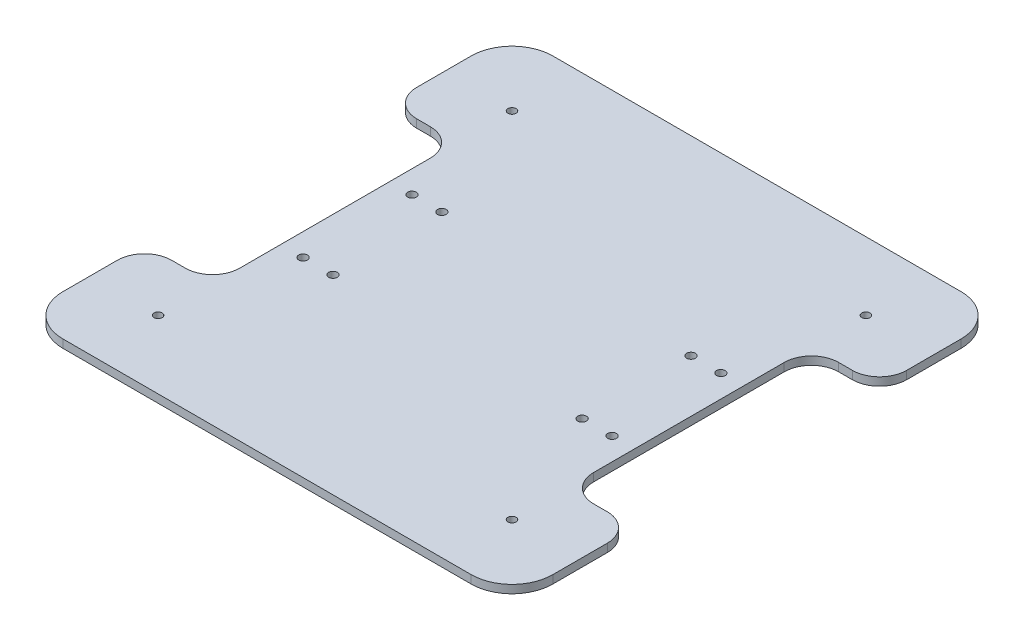
SolidWorks part; units mm, degrees
ref_plane "Спереди" through (0, 0, 0) normal (0, 0, 1) x (1, 0, 0)
ref_plane "Сверху" through (0, 0, 0) normal (0, 1, 0) x (1, 0, 0)
ref_plane "Справа" through (0, 0, 0) normal (1, 0, 0) x (0, 0, -1)
sketch "Sketch1" plane through (0, 0, 0) normal (0, 1, 0) x (1, 0, 0)
  line L1 (-90, 90) -> (90, 90)
  line L2 (-90, 90) -> (-90, -90)
  line L3 (-90, -90) -> (90, -90)
  line L4 (90, 90) -> (90, -90)
  line L5 (-90, 90) -> (90, -90) construction
  line L6 (-90, -90) -> (90, 90) construction
  point P0 (0, 0)
  dimension "D1" = 180
  dimension "D2" = 180
extrude "Boss-Extrude1" add sketch "Sketch1" along normal blind 3
fillet "Fillet1" radius 15 4 edges at (-90, 1.5, -90) (90, 1.5, -90) (-90, 1.5, 90) (90, 1.5, 90)
sketch "Sketch2" plane through (0, 3, 0) normal (0, 1, 0) x (1, 0, 0)
  line L0 (0, 0) -> (-77.5, 0) construction
  line L1 (2.75, 0) -> (-2.75, 0) construction
  line L2 (-90, 75) -> (-90, -75) construction
  line L3 (-90, 45) -> (-65, 45)
  line L4 (-90, 45) -> (-90, -45)
  line L5 (-90, -45) -> (-65, -45)
  line L6 (-65, 45) -> (-65, -45)
  line L7 (-90, 45) -> (-65, -45) construction
  line L8 (-90, -45) -> (-65, 45) construction
  line L9 (0, 0) -> (0, 45) construction
  line L10 (90, -45) -> (65, 45) construction
  line L11 (90, 45) -> (65, -45) construction
  line L12 (65, 45) -> (65, -45)
  line L13 (90, -45) -> (65, -45)
  line L14 (90, 45) -> (90, -45)
  line L15 (90, 45) -> (65, 45)
  circle A0 centre (-56.75, 20) radius 1.6
  circle A1 centre (-45.75, 20) radius 1.6
  circle A2 centre (-56.75, -20) radius 1.6
  circle A3 centre (-45.75, -20) radius 1.6
  circle A4 centre (45.75, 20) radius 1.6
  circle A5 centre (56.75, 20) radius 1.6
  circle A6 centre (45.75, -20) radius 1.6
  circle A7 centre (56.75, -20) radius 1.6
  dimension "D1" = 25
  dimension "D2" = 90
extrude "Cut-Extrude2" cut sketch "Sketch2" against normal through all
fillet "Fillet2" radius 10 8 edges at (-65, 1.5, 45) (-65, 1.5, -45) (65, 1.5, -45) (65, 1.5, 45) (90, 1.5, -45) (90, 1.5, 45) (-90, 1.5, 45) (-90, 1.5, -45)
hole_wizard "Диаметр отверстия Ø3.0 (3)1" positions "Эскиз2" profile "Эскиз1" hole size "Ø3.0" standard "Ansi Metric" end condition up to next
sketch "Эскиз2" plane through (0, 3, 0) normal (0, 1, 0) x (1, 0, 0)
  line L7 (-65, -65) -> (-65, 65) construction
  line L9 (65, 65) -> (65, -65) construction
  line L11 (-90, 65) -> (-65, 65) construction
  line L12 (-90, 75) -> (-90, 55) construction
  line L13 (-65, 65) -> (65, 65) construction
  line L14 (65, 65) -> (90, 65) construction
  line L15 (90, 55) -> (90, 75) construction
  line L17 (90, -65) -> (65, -65) construction
  line L18 (90, -75) -> (90, -55) construction
  line L19 (65, -65) -> (-65, -65) construction
  line L20 (-65, -65) -> (-90, -65) construction
  line L21 (-90, -55) -> (-90, -75) construction
  line L22 (-65, 65) -> (-65, 90) construction
  line L23 (75, 90) -> (-75, 90) construction
  point P15 (-65, -65)
  point P16 (-65, 65)
  point P19 (65, 65)
  point P20 (65, -65)
sketch "Эскиз1" plane through (-65, 3, 65) normal (1, 0, 0) x (0, 0, 1)
  line L0 (0, 0) -> (0, 3)
  line L1 (0, 3) -> (1.5, 3)
  line L2 (1.5, 3) -> (1.5, 0)
  line L5 (1.5, 0) -> (0, 0)
  line L11 (0, -6.35) -> (0, 107.95) construction
  dimension "Диаметр сквозного отверстия" = 3
  dimension "Глубина сквозного отверстия" = 3
